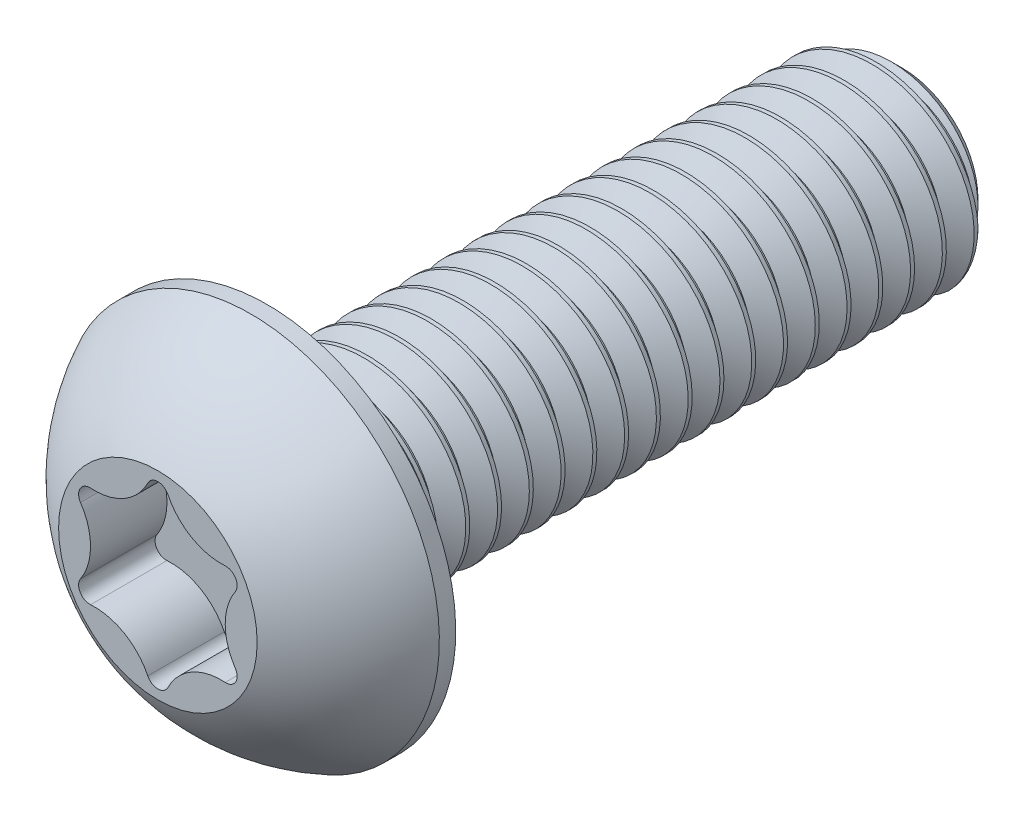
SolidWorks part; units mm, degrees
ref_plane "Front" through (0, 0, 0) normal (0, 0, 1) x (1, 0, 0)
ref_plane "Top" through (0, 0, 0) normal (0, 1, 0) x (1, 0, 0)
ref_plane "Right" through (0, 0, 0) normal (1, 0, 0) x (0, 0, -1)
sketch "Sketch1" plane through (0, 0, 0) normal (1, 0, 0) x (0, 0, -1)
  line L2 (-8, 2.5) -> (8, 2.5)
  line L3 (8, 2.5) -> (8, 0)
  line L4 (8, 0) -> (-8, 0)
  line L6 (-8.4125, 4.75) -> (-8, 4.75) construction
  line L7 (8, 2.5) -> (8, -2.5) construction
  line L8 (-10.75, 0) -> (-8, 0) construction
  line L9 (-8, 4.75) -> (-8, -4.75) construction
  line L11 (-8, 2.5) -> (-8, 0)
  line L14 (-10.75, 0) -> (-10.75, 2.5) construction
  line L15 (8, -2.5) -> (7.2, -2.5) construction
  arc A3 (-10.75, 2.5) -> (-8.4125, 4.75) centre (-6.0919, 0) cw construction
  point P10 (6.8, -2.5)
  point P15 (0, 0)
  dimension "Thread OD" = 5
  dimension "D1" = 0.4125
  dimension "Head Height" = 2.75
  dimension "Head Diameter" = 9.5
  dimension "Length" = 16
  dimension "Thread Pitch" = 0.8
  dimension "D2" = 1.2
sketch "Sketch2" plane through (0, 0, 0) normal (0, 0, 1) x (1, 0, 0)
  line L0 (0, 0) -> (-1.9579, 1.1304)
  line L1 (0, 0) -> (-1.9579, -1.1304)
  line L2 (0, 2.2608) -> (0, 1.9782) construction
  line L3 (0, 1.9782) -> (0, 1.6956) construction
  circle A0 centre (0, 0) radius 2.2608 construction
  circle A1 centre (0, 0) radius 1.6956 construction
  circle A2 centre (0, 0) radius 1.9782 construction
  arc A4 (-1.9481, 0.832) -> (-1.9481, -0.832) centre (-3.1927, 0) cw
  arc A5 (-1.9481, 0.832) -> (-1.9579, 1.1304) centre (-1.7132, 0.9891) cw
  arc A6 (-1.9481, -0.832) -> (-1.9579, -1.1304) centre (-1.7132, -0.9891) ccw
  point P3 (0, -2.2608)
  dimension "Torx OD" = 4.5216
  dimension "D1" = 3.3912
  dimension "D2" = 60
sketch "Sketch12" plane through (0, 0, 0) normal (1, 0, 0) x (0, 0, -1)
  line L0 (-8, 2.5) -> (-8, 0) construction
  line L1 (8, 0) -> (-8, 0) construction
  line L2 (8, 2.5) -> (8, 0) construction
  line L3 (-8, 2.5) -> (8, 2.5) construction
  line L4 (-8, 2.5) -> (-8, 0)
  line L5 (8, 0) -> (-8, 0)
  line L6 (8, 2.5) -> (8, 0)
  line L7 (-8, 2.5) -> (8, 2.5)
revolve "Revolve1" add sketch "Sketch12" angle 360 about L5
sketch "Sketch7" plane through (0, 0, 0) normal (1, 0, 0) x (0, 0, -1)
  line L0 (-10.75, 0) -> (-10.75, 2.5) construction
  line L6 (-8.4125, 4.75) -> (-8, 4.75) construction
  line L8 (-10.75, 0) -> (-8, 0) construction
  line L11 (-8, 4.75) -> (-8, -4.75) construction
  line L12 (-8.4125, 4.75) -> (-8, 4.75)
  line L13 (-10.75, 0) -> (-8, 0)
  line L15 (-8, 4.75) -> (-8, 0)
  line L16 (-10.75, 2.5) -> (-10.75, 0)
  arc A2 (-8.4125, 4.75) -> (-10.75, 2.5) centre (-6.0919, 0) ccw construction
  arc A3 (-8.4125, 4.75) -> (-10.75, 2.5) centre (-6.0919, 0) ccw
revolve "Revolve2" add sketch "Sketch7" angle 360 mid plane about L13
sketch "Sketch11" plane through (0, 0, 10.75) normal (0, 0, 1) x (1, 0, 0)
  line L0 (0, 0) -> (-1.9579, 1.1304) construction
  line L1 (0, 0) -> (-1.9579, -1.1304) construction
  line L2 (0, 0) -> (-1.9579, 1.1304)
  line L3 (0, 0) -> (-1.9579, -1.1304)
  arc A0 (-1.9579, 1.1304) -> (-1.9481, 0.832) centre (-1.7132, 0.9891) ccw construction
  arc A1 (-1.9481, -0.832) -> (-1.9481, 0.832) centre (-3.1927, 0) ccw construction
  arc A3 (-1.9481, -0.832) -> (-1.9579, -1.1304) centre (-1.7132, -0.9891) ccw construction
  arc A4 (-1.9579, 1.1304) -> (-1.9481, 0.832) centre (-1.7132, 0.9891) ccw
  arc A5 (-1.9481, -0.832) -> (-1.9481, 0.832) centre (-3.1927, 0) ccw
  arc A7 (-1.9481, -0.832) -> (-1.9579, -1.1304) centre (-1.7132, -0.9891) ccw
extrude "Cut-Extrude4" cut sketch "Sketch11" against normal blind 1.925
pattern_circular "CirPattern1" count 6 over 360 of "Cut-Extrude4"
chamfer "Chamfer1" distance 0.6 angle 45 1 edges at (0, 2.5, -8)
split "Split1" bodies to split 122 113 resulting bodies 125 126 split by face at (0, -2.5, 8)
sketch "Sketch13" plane through (0, 0, -8) normal (0, 0, -1) x (-1, 0, 0)
  circle A0 centre (0, 0) radius 2.5 construction
  circle A1 centre (0, 0) radius 2.5
curve "Helix/Spiral1" pitch 0.8 height 16.8 radius 2.5 centre (0, 0, -8) axis (0, 0, 1) start towards (0, 1, 0)
sketch "Sketch14" plane through (0, 0, 0) normal (1, 0, 0) x (0, 0, -1)
  line L0 (8.75, 2.5866) -> (7.95, 2.5866) construction
  line L1 (7.95, 2.5866) -> (8.35, 1.8938) construction
  line L2 (8.35, 1.8938) -> (8.75, 2.5866) construction
  line L3 (8.7, 2.5) -> (8, 2.5) construction
  line L4 (8.35, 2.5866) -> (8.35, 2.5) construction
  line L5 (8.725, 2.5433) -> (7.975, 2.5433) construction
  line L6 (8.4, 1.9804) -> (8.3, 1.9804) construction
  line L7 (8.35, 1.9804) -> (8.35, 1.8938) construction
  line L8 (8.3, 1.9804) -> (7.975, 2.5433)
  line L9 (7.975, 2.5433) -> (8.725, 2.5433)
  line L10 (8.725, 2.5433) -> (8.4, 1.9804)
  line L11 (8.4, 1.9804) -> (8.3, 1.9804)
  point P11 (8.35, 2.5433)
  dimension "D1" = 0.8
  dimension "D2" = 0.1
sweep "Cut-Sweep1" cut profiles "Sketch14" path "Helix/Spiral1" align with end faces yes
combine bodies "Combine1" operation type add bodies to combine 125 127
equation "\"D3@Helix/Spiral1\" = \"Length@Sketch1\" + \"Thread Pitch@Sketch1\""
equation "\"D1@Chamfer1\"=\"D4@Helix/Spiral1\" * .75"
equation "\"D1@Sketch1\" = \"Head Height@Sketch1\" * .15"
equation "\"D1@Cut-Extrude4\" = \"Head Height@Sketch1\" * .7"
equation "\"D2@Sketch1\"=\"Thread Pitch@Sketch1\"*1.5"
equation "\"D1@Sketch14\"=\"Thread Pitch@Sketch1\""
equation "\"D2@Sketch14\"=\"D1@Sketch14\"/ 1/8"
equation "\"D4@Helix/Spiral1\"=\"Thread Pitch@Sketch1\""
equation "\"D1@Sketch2\"=\"Torx OD@Sketch2\"*.75"
